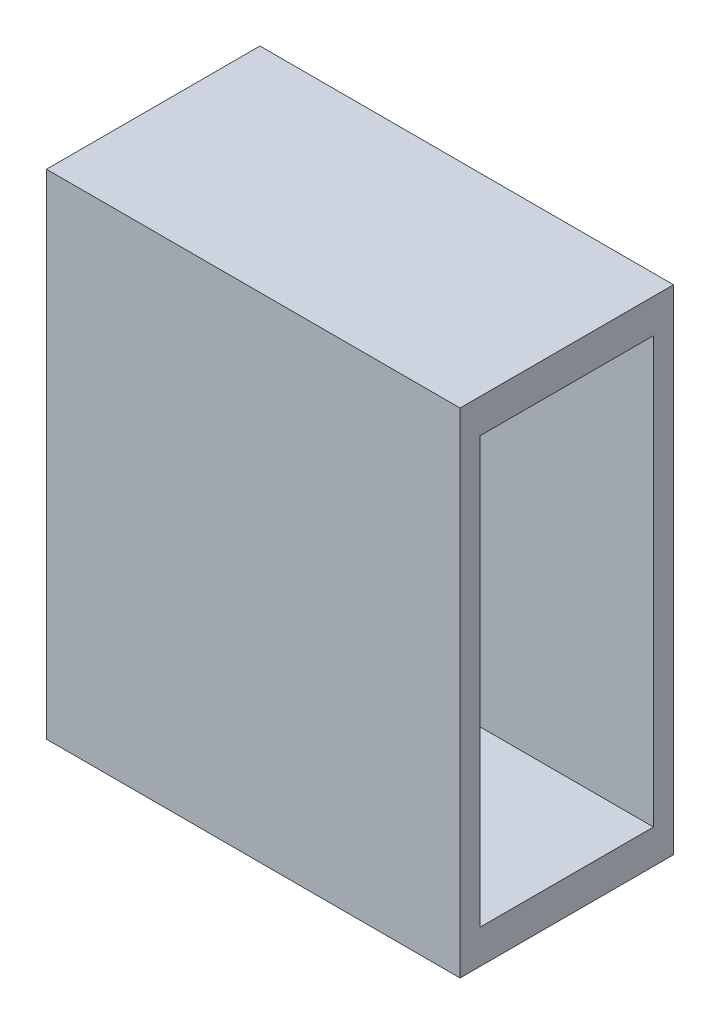
SolidWorks part; units mm, degrees
ref_plane "Front Plane" through (0, 0, 0) normal (1, 0, 0) x (0, 1, 0)
ref_plane "Top Plane" through (0, 0, 0) normal (0, 0, 1) x (0, 1, 0)
ref_plane "Right Plane" through (0, 0, 0) normal (0, 1, 0) x (-1, 0, 0)
sketch "Sketch1" plane through (0, 0, 0) normal (1, 0, 0) x (0, 1, 0)
  line L5 (-37, 8) -> (-30.25, 8) construction
  line L6 (-37, 16) -> (0, 16)
  line L11 (-37, 16) -> (-37, 0)
  line L12 (-37, 0) -> (0, 0)
  line L20 (0, 16) -> (0, 0)
  line L21 (-30.25, 14.5) -> (-6.75, 14.5)
  line L22 (-30.25, 14.5) -> (-30.25, 1.5)
  line L23 (-30.25, 1.5) -> (-6.75, 1.5)
  line L24 (-6.75, 14.5) -> (-6.75, 1.5)
  line L25 (-6.75, 8) -> (0, 8) construction
  line L26 (-18.5, 0) -> (-18.5, 1.5) construction
  line L27 (-18.5, 16) -> (-18.5, 14.5) construction
  line L29 (-34.45, 1.5) -> (-2.55, 1.5)
  line L30 (-34.45, 1.5) -> (-34.45, 14.5)
  line L31 (-34.45, 14.5) -> (-2.55, 14.5)
  line L32 (-2.55, 1.5) -> (-2.55, 14.5)
  dimension "D1" = 4.2
  dimension "D2" = 13
  dimension "D3" = 4.2
  dimension "D6" = 37
  dimension "D7" = 23.5
  dimension "D9" = 1.5
extrude "Boss-Extrude1" add sketch "Sketch1" along normal blind 26 contours L20 L6 L11 L12 L21 L24 L23 L22 region at (0, -18.5, 15.5969)
extrude "Boss-Extrude2" add sketch "Sketch1<3>" along normal blind 2 contours L31 L30 L29 L22 | L29 L32 L31 L24 region at (0, -32.35, 8) region at (0, -4.65, 8)
sketch "Sketch1<3>" plane through (0, 0, 0) normal (1, 0, 0) x (0, 1, 0) same geometry as "Sketch1"
sketch "Sketch2" plane through (26, 0, 0) normal (1, 0, 0) x (0, 1, 0)
  line L1 (-37, 16) -> (0, 16)
  line L2 (-37, 16) -> (-37, 0)
  line L3 (-37, 0) -> (0, 0)
  line L4 (0, 16) -> (0, 0)
sketch "Sketch3" plane through (0, 0, 0) normal (-1, 0, 0) x (0, -1, 0)
  line L1 (0, 16) -> (37, 16)
  line L2 (0, 16) -> (0, 0)
  line L3 (0, 0) -> (37, 0)
  line L4 (37, 16) -> (37, 0)
  line L5 (2.55, 14.5) -> (34.45, 14.5)
  line L6 (2.55, 14.5) -> (2.55, 1.5)
  line L7 (2.55, 1.5) -> (34.45, 1.5)
  line L8 (34.45, 14.5) -> (34.45, 1.5)
extrude "Boss-Extrude4" add sketch "Sketch3" along normal blind 3.5
sketch "Sketch5" plane through (-3.5, 0, 0) normal (-1, 0, 0) x (0, -1, 0)
  line L0 (37, 8) -> (30.25, 8) construction
  line L1 (0, 16) -> (37, 16)
  line L2 (0, 16) -> (0, 0)
  line L3 (0, 0) -> (37, 0)
  line L4 (37, 16) -> (37, 0)
  line L5 (30.25, 14.5) -> (30.25, 1.5) construction
  circle A0 centre (23.25, 8) radius 5.2
  dimension "D1" = 10.4
  dimension "D2" = 7
extrude "Boss-Extrude5" add sketch "Sketch5" along normal blind 1.5
ref_plane "Plane1" through (26, 0, 16) normal (0, 0, -1) x (-1, 0, 0)
sketch "Sketch9" plane through (0, 0, 0) normal (0, 1, 0) x (-1, 0, 0)
  line L0 (-26, 8) -> (5, 8) construction
  line L3 (-26, 16) -> (-26, 0) construction
  line L4 (5, 16) -> (5, 0) construction
  line L5 (-2, 5.65) -> (-17, 4.4)
  line L6 (-2, 10.35) -> (-17, 11.6)
  circle A2 centre (-17, 8) radius 3.6
  circle A3 centre (-2, 8) radius 2.35
  circle A4 centre (-17, 8) radius 0.15
  circle A5 centre (-2, 8) radius 0.15
  point P4 (-2, 8)
  dimension "D1" = 0.3
  dimension "D4" = 7.2
  dimension "D5" = 4.7
  dimension "D6" = 15
  dimension "D7" = 9
sketch "Sketch10" plane through (0, 0, 16) normal (0, 0, 1) x (1, 0, 0)
sketch "Sketch11" plane through (0, -37, 0) normal (0, -1, 0) x (1, 0, 0)
  line L0 (3.625, 8) -> (18.625, 8) construction
  line L1 (18.625, 5.65) -> (3.625, 4.4)
  line L2 (18.625, 10.35) -> (3.625, 11.6)
  line L3 (-5, 8) -> (0.025, 8) construction
  line L4 (-5, 0) -> (-5, 16) construction
  line L5 (20.975, 8) -> (26, 8) construction
  line L6 (26, 16) -> (26, 0) construction
  line L7 (3.625, 11.6) -> (3.625, 16) construction
  line L8 (26, 16) -> (-5, 16) construction
  line L9 (3.625, 0) -> (3.625, 4.4) construction
  line L10 (26, 0) -> (-5, 0) construction
  circle A0 centre (3.625, 8) radius 3.6
  circle A1 centre (18.625, 8) radius 2.35
  circle A2 centre (3.625, 8) radius 0.15
  circle A3 centre (18.625, 8) radius 0.15
  dimension "D1" = 7.2
  dimension "D2" = 4.7
  dimension "D4" = 0.3
  dimension "D3" = 15
extrude "Cut-Extrude5" cut sketch "Sketch11" against normal blind 1.5 contours A1 L2 A0 L1 | A1 A3 | L1 A0 L2 A2 | A3 | A2 region at (11.4276, -37, 8) region at (16.3415, -37, 8) region at (3.9145, -37, 4.5263) region at (3.625, -37, 8) region at (18.625, -37, 8)
extrude "Cut-Extrude12" cut sketch "Sketch11<7>" against normal blind 2 contours A2 | A3 region at (3.625, -37, 8) region at (18.625, -37, 8)
sketch "Sketch11<7>" plane through (0, -37, 0) normal (0, -1, 0) x (1, 0, 0) same geometry as "Sketch11"
